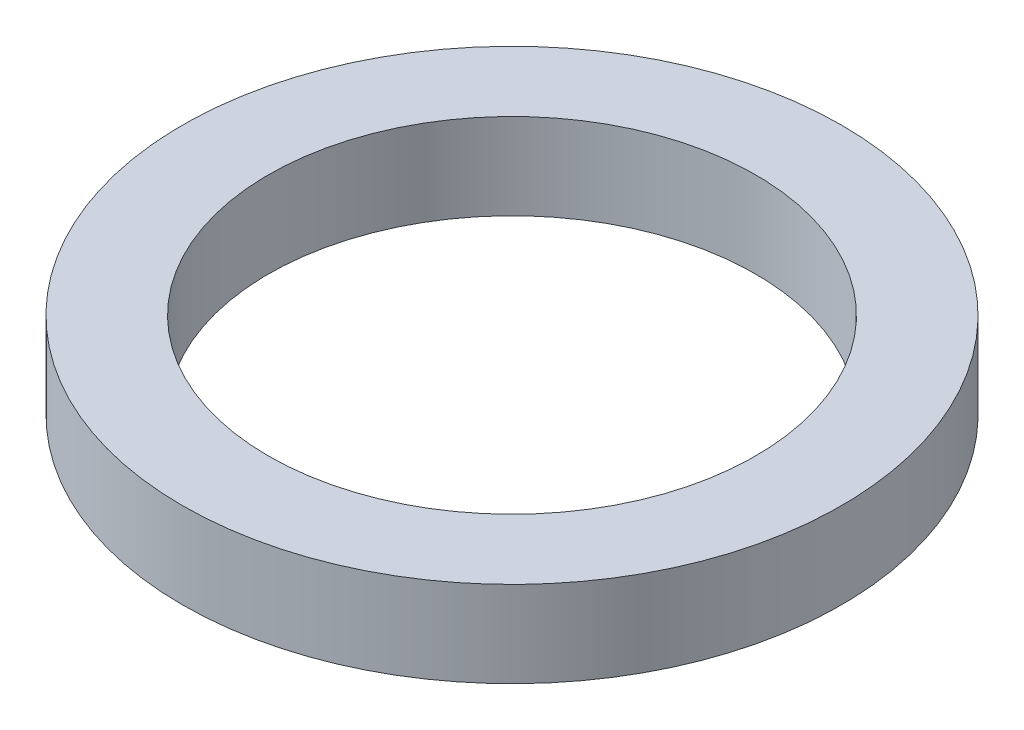
SolidWorks part; units mm, degrees
ref_plane "Front Plane" through (0, 0, 0) normal (0, 0, 1) x (1, 0, 0)
ref_plane "Top Plane" through (0, 0, 0) normal (0, 1, 0) x (1, 0, 0)
ref_plane "Right Plane" through (0, 0, 0) normal (1, 0, 0) x (0, 0, -1)
sketch "Sketch1" plane through (0, 0, 0) normal (0, 1, 0) x (1, 0, 0)
  circle A0 centre (0, 0) radius 57.5
  dimension "FLANGE_OD" = 115
extrude "Boss-Extrude1" add sketch "Sketch1" along normal blind 15
sketch "Sketch2" plane through (0, 0, 0) normal (0, 1, 0) x (1, 0, 0)
  circle A0 centre (0, 0) radius 42.5
  dimension "BORE_D" = 85
extrude "Cut-Extrude1" cut sketch "Sketch2" along normal through all
sketch "Sketch3" plane through (0, 15, 0) normal (0, 1, 0) x (1, 0, 0)
  circle A0 centre (0, 0) radius 24.7214 construction
  circle A1 centre (-24.7214, 0) radius 1.5473
  dimension "BOLT_D" = 3.0946
  dimension "BOLT_PCD" = 49.4428
extrude "Cut-Extrude2" cut sketch "Sketch3" against normal blind 9.6208 rebuild error yes
pattern_circular "CirPattern1" count 4 over 360 rebuild error yes
